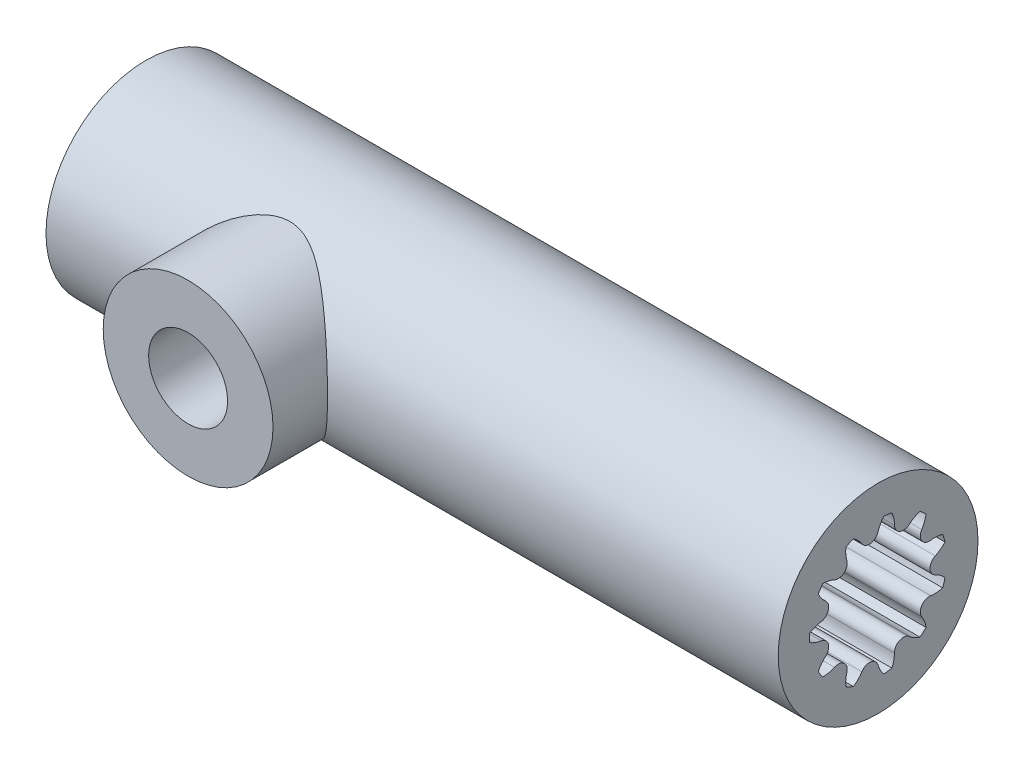
SolidWorks part; units mm, degrees
ref_plane "Front Plane" through (0, 0, 0) normal (1, 0, 0) x (0, 1, 0)
ref_plane "Top Plane" through (0, 0, 0) normal (0, 0, 1) x (0, 1, 0)
ref_plane "Right Plane" through (0, 0, 0) normal (0, 1, 0) x (-1, 0, 0)
sketch "Sketch1" plane through (0, 0, 0) normal (1, 0, 0) x (0, 1, 0)
  line L0 (-2.0767, 2.5) -> (2.0767, 2.5)
  circle A0 centre (0, 0) radius 3.25 construction
  circle A1 centre (0, 0) radius 5.5
  circle A2 centre (0, 0) radius 3.05
  dimension "D1" = 0.2
  dimension "D2" = 6.1
  dimension "D4" = 11
  dimension "D3" = 2.5
extrude "Boss-Extrude1" add sketch "Sketch1" along normal blind 14 contours A1 A2 | L0 A2 region at (0, 0, 2.7218) region at (0, -5.3444, 0)
sketch "Sketch2" plane through (14, 0, 0) normal (1, 0, 0) x (0, 1, 0)
  circle A0 centre (0, 0) radius 5.5
  circle A1 centre (0, 0) radius 5.5 construction
extrude "Boss-Extrude2" add sketch "Sketch2" along normal blind 13.52
sketch "Sketch3" plane through (27.52, 0, 0) normal (1, 0, 0) x (0, 1, 0)
  circle A0 centre (0, 0) radius 3.84 construction
  arc A1 (-1.322, -2.893) -> (-1.3171, -2.8446) centre (-1.8115, -2.8187) ccw
  arc A2 (-0.4299, -3.1051) -> (-0.4519, -3.1485) centre (0, -3.3506) ccw
  arc A3 (0.4299, -3.1051) -> (-0.4299, -3.1051) centre (0, -3.3506) ccw
  arc A4 (0.4519, -3.1485) -> (0.4299, -3.1051) centre (0, -3.3506) ccw
  arc A5 (1.3171, -2.8446) -> (1.322, -2.893) centre (1.8115, -2.8187) ccw
  arc A6 (2.0824, -2.4044) -> (2.0404, -2.3797) centre (1.8115, -2.8187) ccw
  arc A7 (3.0517, -0.8968) -> (3.0031, -0.8989) centre (3.0478, -1.3919) ccw
  arc A8 (2.6459, -1.6809) -> (2.6762, -1.719) centre (3.0478, -1.3919) ccw
  arc A9 (3.1347, 0.0164) -> (3.1808, 0.0008) centre (3.3165, 0.4768) ccw
  arc A10 (3.0521, 0.8954) -> (3.0123, 0.8674) centre (3.3165, 0.4768) ccw
  arc A11 (3.0517, -0.8968) -> (3.7011, -0.7578) centre (3.0638, 0.6324) ccw
  arc A12 (3.0031, -0.8989) -> (2.6459, -1.6809) centre (3.0478, -1.3919) ccw
  arc A13 (2.9964, -2.3008) -> (2.6762, -1.719) centre (1.5285, -2.7296) ccw
  arc A14 (2.7039, -2.6385) -> (2.9964, -2.3008) centre (0, 0) ccw
  arc A15 (2.0824, -2.4044) -> (2.7039, -2.6385) centre (2.9193, -1.1245) ccw
  arc A16 (2.0404, -2.3797) -> (1.3171, -2.8446) centre (1.8115, -2.8187) ccw
  arc A17 (1.2768, -3.5556) -> (1.322, -2.893) centre (-0.1899, -3.1226) ccw
  arc A18 (0.8482, -3.6814) -> (1.2768, -3.5556) centre (0, 0) ccw
  arc A19 (0.4519, -3.1485) -> (0.8482, -3.6814) centre (1.848, -2.5243) ccw
  arc A20 (-0.8482, -3.6814) -> (-0.4519, -3.1485) centre (-1.848, -2.5243) ccw
  arc A21 (-1.2768, -3.5556) -> (-0.8482, -3.6814) centre (0, 0) ccw
  arc A22 (-1.322, -2.893) -> (-1.2768, -3.5556) centre (0.1899, -3.1226) ccw
  arc A23 (3.7011, -0.7578) -> (3.7647, -0.3156) centre (0, 0) ccw
  arc A24 (3.7647, -0.3156) -> (3.1808, 0.0008) centre (2.7616, -1.4699) ccw
  arc A25 (3.0123, 0.8674) -> (3.1347, 0.0164) centre (3.3165, 0.4768) ccw
  arc A26 (3.0521, 0.8954) -> (3.5232, 1.3635) centre (2.2356, 2.1884) ccw
  arc A27 (3.5232, 1.3635) -> (3.3377, 1.7698) centre (0, 0) ccw
  arc A28 (-2.0404, -2.3797) -> (-2.0824, -2.4044) centre (-1.8115, -2.8187) ccw
  arc A29 (-2.6762, -1.719) -> (-2.6459, -1.6809) centre (-3.0478, -1.3919) ccw
  arc A30 (-3.0031, -0.8989) -> (-3.0517, -0.8968) centre (-3.0478, -1.3919) ccw
  arc A31 (-3.1808, 0.0008) -> (-3.1347, 0.0164) centre (-3.3165, 0.4768) ccw
  arc A32 (-3.0123, 0.8674) -> (-3.0521, 0.8954) centre (-3.3165, 0.4768) ccw
  arc A33 (-1.3171, -2.8446) -> (-2.0404, -2.3797) centre (-1.8115, -2.8187) ccw
  arc A34 (-2.7039, -2.6385) -> (-2.0824, -2.4044) centre (-2.9193, -1.1245) ccw
  arc A35 (-2.9964, -2.3008) -> (-2.7039, -2.6385) centre (0, 0) ccw
  arc A36 (-2.6762, -1.719) -> (-2.9964, -2.3008) centre (-1.5285, -2.7296) ccw
  arc A37 (-2.6459, -1.6809) -> (-3.0031, -0.8989) centre (-3.0478, -1.3919) ccw
  arc A38 (-3.7011, -0.7578) -> (-3.0517, -0.8968) centre (-3.0638, 0.6324) ccw
  arc A39 (-3.7647, -0.3156) -> (-3.7011, -0.7578) centre (0, 0) ccw
  arc A40 (-3.1808, 0.0008) -> (-3.7647, -0.3156) centre (-2.7616, -1.4699) ccw
  arc A41 (-3.1347, 0.0164) -> (-3.0123, 0.8674) centre (-3.3165, 0.4768) ccw
  arc A42 (-3.5232, 1.3635) -> (-3.0521, 0.8954) centre (-2.2356, 2.1884) ccw
  arc A43 (-2.6754, 1.7203) -> (-2.6282, 1.7085) centre (-2.5322, 2.1942) ccw
  arc A44 (-2.0651, 2.3583) -> (-2.0835, 2.4034) centre (-2.5322, 2.1942) ccw
  arc A45 (-1.3207, 2.8936) -> (-1.2873, 2.8582) centre (-0.944, 3.2148) ccw
  arc A46 (-0.4623, 3.1004) -> (-0.4534, 3.1483) centre (-0.944, 3.2148) ccw
  arc A47 (2.6282, 1.7085) -> (2.6754, 1.7203) centre (2.5322, 2.1942) ccw
  arc A48 (2.0835, 2.4034) -> (2.0651, 2.3583) centre (2.5322, 2.1942) ccw
  arc A49 (3.3377, 1.7698) -> (2.6754, 1.7203) centre (3.1179, 0.2564) ccw
  arc A50 (2.0651, 2.3583) -> (2.6282, 1.7085) centre (2.5322, 2.1942) ccw
  arc A51 (2.0835, 2.4034) -> (2.2268, 3.0518) centre (0.6976, 3.0497) ccw
  arc A52 (2.2268, 3.0518) -> (1.851, 3.2933) centre (0, 0) ccw
  arc A53 (1.2873, 2.8582) -> (1.3207, 2.8936) centre (0.944, 3.2148) ccw
  arc A54 (0.4534, 3.1483) -> (0.4623, 3.1004) centre (0.944, 3.2148) ccw
  arc A55 (1.851, 3.2933) -> (1.3207, 2.8936) centre (2.4843, 1.9014) ccw
  arc A56 (0.4623, 3.1004) -> (1.2873, 2.8582) centre (0.944, 3.2148) ccw
  arc A57 (0.4534, 3.1483) -> (0.2234, 3.7713) centre (-1.0619, 2.9427) ccw
  arc A58 (0.2234, 3.7713) -> (0, 3.7779) centre (0, 0) ccw
  arc A59 (0, 3.7779) -> (-0.2234, 3.7713) centre (0, 0) ccw
  arc A60 (-0.2234, 3.7713) -> (-0.4534, 3.1483) centre (1.0619, 2.9427) ccw
  arc A61 (-1.2873, 2.8582) -> (-0.4623, 3.1004) centre (-0.944, 3.2148) ccw
  arc A62 (-1.3207, 2.8936) -> (-1.851, 3.2933) centre (-2.4843, 1.9014) ccw
  arc A63 (-1.851, 3.2933) -> (-2.2268, 3.0518) centre (0, 0) ccw
  arc A64 (-2.2268, 3.0518) -> (-2.0835, 2.4034) centre (-0.6976, 3.0497) ccw
  arc A65 (-2.6282, 1.7085) -> (-2.0651, 2.3583) centre (-2.5322, 2.1942) ccw
  arc A66 (-2.6754, 1.7203) -> (-3.3377, 1.7698) centre (-3.1179, 0.2564) ccw
  arc A67 (-3.3377, 1.7698) -> (-3.5232, 1.3635) centre (0, 0) ccw
  circle A68 centre (0, 0) radius 5.5
  circle A69 centre (0, 0) radius 5.5 construction
  point P3 (0, 1.6)
extrude "Boss-Extrude3" add sketch "Sketch3" along normal blind 12.8
sketch "Sketch4" plane through (27.52, 0, 0) normal (1, 0, 0) x (0, 1, 0)
  circle A0 centre (0, 0) radius 1.05
  dimension "D1" = 2.1
extrude "Cut-Extrude1" cut sketch "Sketch4" against normal blind 3.5
sketch "Sketch5" plane through (0, 0, 2.5) normal (0, 0, -1) x (-1, 0, 0)
  line L0 (-14, 0) -> (0, 0) construction
  line L4 (0, -1.7471) -> (0, 1.7471)
  line L5 (0, 1.7471) -> (-14, 1.7471)
  line L6 (-14, 1.7471) -> (-14, -1.7471)
  line L7 (-14, -1.7471) -> (0, -1.7471)
  line L8 (0, -1.7471) -> (0, 1.7471) construction
  line L9 (0, 1.7471) -> (-14, 1.7471) construction
  line L10 (-14, 1.7471) -> (-14, -1.7471) construction
  line L11 (-14, -1.7471) -> (0, -1.7471) construction
  circle A0 centre (-10.825, 0) radius 2.175
  circle A1 centre (-10.825, 0) radius 4.675
  point P10 (0, 0)
  dimension "D2" = 1
  dimension "D3" = 4.35
  dimension "D1" = 0
  dimension "D4" = 2.5
extrude "Boss-Extrude4" add sketch "Sketch5" against normal blind 6
extrude "Cut-Extrude2" cut sketch "Sketch5<2>" against normal through all contours A0
sketch "Sketch5<2>" plane through (0, 0, 2.5) normal (0, 0, -1) x (-1, 0, 0) same geometry as "Sketch5"
